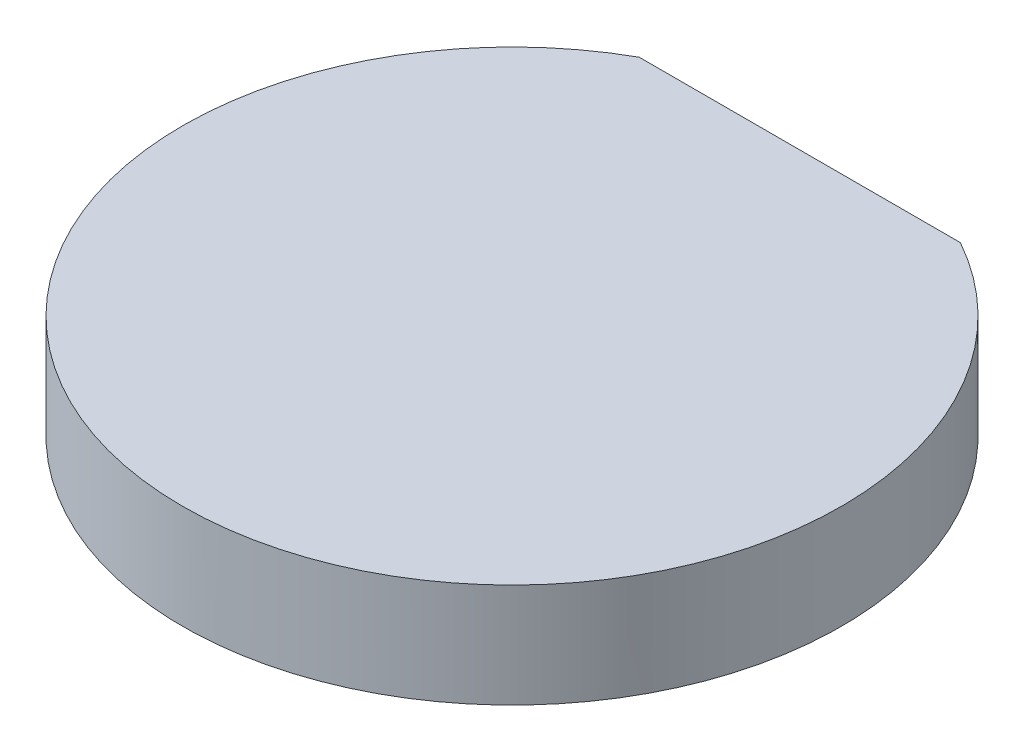
SolidWorks part; units mm, degrees
ref_plane "Front Plane" through (0, 0, 0) normal (0, 0, 1) x (1, 0, 0)
ref_plane "Top Plane" through (0, 0, 0) normal (0, 1, 0) x (1, 0, 0)
ref_plane "Right Plane" through (0, 0, 0) normal (1, 0, 0) x (0, 0, -1)
sketch "Sketch1" plane through (0, 0, 0) normal (0, -1, 0) x (1, 0, 0)
  circle A0 centre (0, -8) radius 35.5
  dimension "D1" = 71
extrude "Boss-Extrude1" add sketch "Sketch1" along normal blind 2
sketch "Sketch2" plane through (0, -2, 0) normal (0, -1, 0) x (1, 0, 0)
  circle A0 centre (0, -8) radius 34
  circle A2 centre (0, -8) radius 35.5 construction
  circle A3 centre (0, -8) radius 35.5
  dimension "D1" = 1.5
extrude "Boss-Extrude2" add sketch "Sketch2" along normal blind 9.2
sketch "Sketch5" plane through (0, -2, 0) normal (0, -1, 0) x (1, 0, 0)
  circle A0 centre (0, -8) radius 34 construction
  circle A1 centre (0, -8) radius 34
  circle A2 centre (0, -8) radius 28.75
  dimension "D1" = 57.5
extrude "Boss-Extrude3" add sketch "Sketch5" along normal blind 1.5
sketch "Sketch3" plane through (0, 0, 0) normal (0, 1, 0) x (1, 0, 0)
  line L0 (-17.2988, 39) -> (17.2988, 39)
  line L1 (0, 42.3765) -> (0, -3.4902) construction
  circle A0 centre (0, 8) radius 35.5 construction
  arc A1 (17.2988, 39) -> (-17.2988, 39) centre (0, 8) ccw
  point P7 (0, -27.5)
  dimension "D1" = 66.5
extrude "Cut-Extrude2" cut sketch "Sketch3" against normal up to next
sketch "Sketch6" plane through (0, -2, 0) normal (0, -1, 0) x (1, 0, 0)
  line L0 (-18.8695, -39) -> (-16, -31.8865)
  line L1 (-16, -31.8865) -> (16, -31.8865)
  line L2 (16, -31.8865) -> (18.8695, -39)
  line L3 (18.8695, -39) -> (-18.8695, -39)
  line L4 (-13.9642, -39) -> (13.9642, -39) construction
  circle A0 centre (0, -8) radius 28.75 construction
  circle A1 centre (0, -8) radius 28.75 construction
  arc A2 (13.9642, -39) -> (-13.9642, -39) centre (0, -8) ccw construction
  point P4 (0, -39)
  point P7 (0, -39)
  point P8 (0, 0)
  point P15 (-18, -36.8444)
  point P17 (18, -36.8444)
  dimension "D1" = 32
  dimension "D2" = 36
extrude "Cut-Extrude3" cut sketch "Sketch6" along normal up to next
